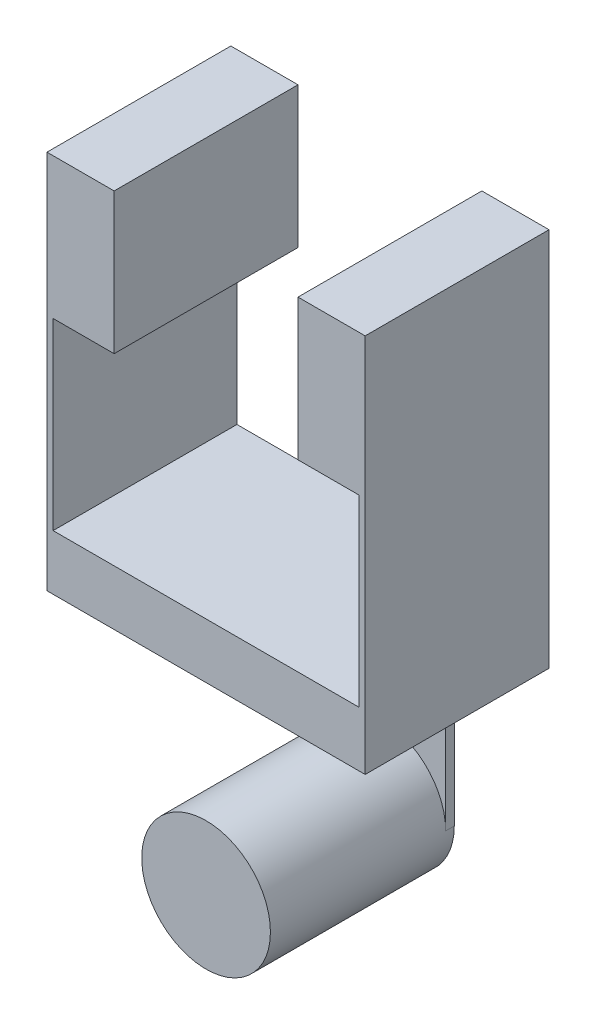
SolidWorks part; units mm, degrees
ref_plane "Front Plane" through (0, 0, 0) normal (0, 0, 1) x (1, 0, 0)
ref_plane "Top Plane" through (0, 0, 0) normal (0, 1, 0) x (1, 0, 0)
ref_plane "Right Plane" through (0, 0, 0) normal (1, 0, 0) x (0, 0, -1)
sketch "Sketch1" plane through (0, 0, 0) normal (0, 0, 1) x (1, 0, 0)
  circle A0 centre (0, 0) radius 13.335
  dimension "D1" = 26.67
extrude "FeatureA" add sketch "Sketch1" against normal blind 38.1 contours A0
ref_plane "Plane1" through (0, 0, -38.1) normal (0, 0, -1) x (-1, 0, 0)
sketch "Sketch2" plane through (0, 0, -38.1) normal (0, 0, -1) x (-1, 0, 0)
  line L0 (-13.335, 0) -> (13.335, 0)
  line L1 (13.335, 0) -> (13.335, 38.1)
  line L2 (13.335, 38.1) -> (-13.335, 38.1)
  line L3 (-13.335, 38.1) -> (-13.335, 0)
  circle A0 centre (0, 0) radius 13.335 construction
  dimension "D1" = 38.1
extrude "FeatureB" add sketch "Sketch2" against normal blind 1.778 contours L2 L3 L0 L1
ref_plane "Plane2" through (0, 38.1, 0) normal (0, 1, 0) x (1, 0, 0)
sketch "Sketch3" plane through (0, 38.1, 0) normal (0, 1, 0) x (1, 0, 0)
  line L0 (0, 38.1) -> (-32.9692, 38.1)
  line L1 (14.6685, 38.1) -> (-14.6685, 38.1) construction
  line L2 (-32.9692, 38.1) -> (-32.9692, 0)
  line L3 (-32.9692, 0) -> (32.9692, 0)
  line L4 (32.9692, 0) -> (32.9692, 38.1)
  line L5 (32.9692, 38.1) -> (0, 38.1)
  line L6 (32.9692, 19.05) -> (-32.9692, 19.05) construction
  line L9 (0, 38.1) -> (0, 0) construction
  dimension "D1" = 65.9384
  dimension "D2" = 38.1
extrude "FeatureC" add sketch "Sketch3" along normal blind 11.43
sketch "Sketch4" plane through (0, 49.53, 0) normal (0, 1, 0) x (1, 0, 0)
  line L0 (34.5757, 38.1) -> (-34.5757, 38.1) construction
  line L1 (32.9692, 0) -> (31.6992, 0)
  line L2 (32.9692, 0) -> (32.9692, 38.1)
  line L3 (32.9692, 38.1) -> (31.6992, 38.1)
  line L4 (31.6992, 0) -> (31.6992, 38.1)
  line L5 (0, 38.1) -> (0, 0) construction
  line L6 (32.9692, 38.1) -> (-32.9692, 38.1) construction
  line L7 (-32.9692, 0) -> (32.9692, 0) construction
  line L8 (-32.9692, 38.1) -> (-31.6992, 38.1)
  line L9 (-31.6992, 0) -> (-31.6992, 38.1)
  line L10 (-32.9692, 0) -> (-31.6992, 0)
  line L11 (-32.9692, 0) -> (-32.9692, 38.1)
  dimension "D1" = 1.27
extrude "FeatureD" add sketch "Sketch4" along normal blind 38.0746
sketch "Sketch7" plane through (0, 87.6046, 0) normal (0, 1, 0) x (1, 0, 0)
  line L0 (36.2661, 38.1) -> (-36.2661, 38.1) construction
  line L1 (32.9692, 0) -> (19.05, 0)
  line L2 (32.9692, 0) -> (32.9692, 38.1)
  line L3 (32.9692, 38.1) -> (19.05, 38.1)
  line L4 (19.05, 0) -> (19.05, 38.1)
  line L5 (31.6992, 38.1) -> (31.6992, 0) construction
  line L6 (0, 0) -> (0, 41.6455) construction
  line L7 (-32.9692, 38.1) -> (-19.05, 38.1)
  line L8 (-19.05, 0) -> (-19.05, 38.1)
  line L9 (-32.9692, 0) -> (-19.05, 0)
  line L10 (-32.9692, 0) -> (-32.9692, 38.1)
  dimension "D1" = 12.6492
extrude "Boss-Extrude5" add sketch "Sketch7" along normal blind 29.21
ref_plane "Plane3" through (0, 87.63, 0) normal (0, 1, 0) x (1, 0, 0)
equation "\"La\"= 1.5"
equation "\"Da\"= 1.05"
equation "\"Wb\"= \"La\""
equation "\"Lb\"= \"La\""
equation "\"tb\"= 0.07"
equation "\"bc\"= 0.498 + 0.9992 * 2"
equation "\"Lc\"= \"La\""
equation "\"hc\"= 0.45"
equation "\"hd\"= 1.499"
equation "\"Ld\"= \"La\""
equation "\"td\"= 0.05"
equation "\"be\"= 0.498"
equation "\"Le\"= \"La\""
equation "\"he\"= 1.15"
equation "\"E\"= 29 * 10 ^ 6"
equation "\"Sy\"= 36000"
equation "\"deflection\"= 0.005"
